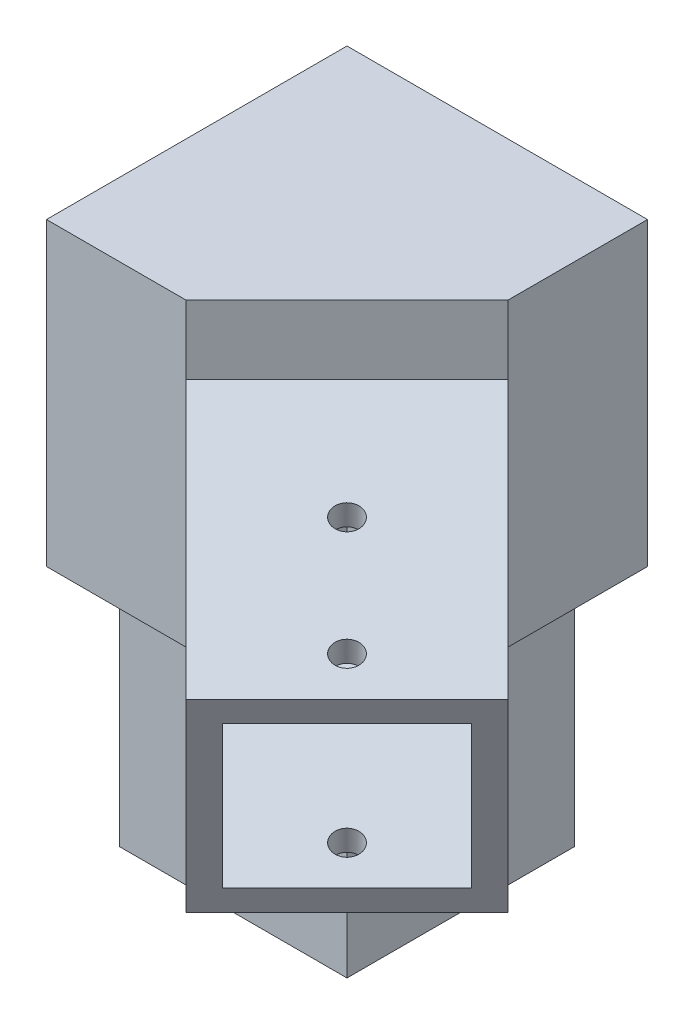
SolidWorks part; units mm, degrees
ref_plane "前视基准面" through (0, 0, 0) normal (0, 0, 1) x (1, 0, 0)
ref_plane "上视基准面" through (0, 0, 0) normal (0, 1, 0) x (1, 0, 0)
ref_plane "右视基准面" through (0, 0, 0) normal (1, 0, 0) x (0, 0, -1)
other "Configuration Table"
sketch "草图2" plane through (0, 0, 0) normal (1, 0, 0) x (0, 0, -1)
  line L0 (0, 0) -> (-60, 0)
  line L1 (-60, 0) -> (-60, -20)
  dimension "D1" = 60
  dimension "D2" = 20
ref_plane "基准面1" through (0, 0, 60) normal (0, 0, 1) x (1, 0, 0)
sketch "草图3" plane through (0, 0, 60) normal (0, 0, 1) x (1, 0, 0)
  line L0 (0, -20) -> (60, -20)
  line L1 (0, 0) -> (0, -20) construction
  line L2 (0, 0) -> (50000, 0) construction
  dimension "D1" = 20
  dimension "D2" = 60
sketch3d "3D草图1"
  line L0 (0, 0, 0) -> (60, -20, 60)
  line L1 (0, 0, 0) -> (0, -20, 0)
  dimension "D1" = 20
sketch "草图4" plane through (0, 0, 0) normal (0, 1, 0) x (1, 0, 0)
  line L1 (-10.25, 10.25) -> (10.25, 10.25)
  line L2 (-10.25, 10.25) -> (-10.25, -10.25)
  line L3 (-10.25, -10.25) -> (10.25, -10.25)
  line L4 (10.25, 10.25) -> (10.25, -10.25)
  line L5 (-10.25, 10.25) -> (10.25, -10.25) construction
  line L6 (-10.25, -10.25) -> (10.25, 10.25) construction
  line L7 (-13.25, 13.25) -> (13.25, 13.25)
  line L8 (-13.25, 13.25) -> (-13.25, -13.25)
  line L9 (-13.25, -13.25) -> (13.25, -13.25)
  line L10 (13.25, 13.25) -> (13.25, -13.25)
  line L11 (-13.25, 13.25) -> (13.25, -13.25) construction
  line L12 (-13.25, -13.25) -> (13.25, 13.25) construction
  point P0 (0, 0)
  point P6 (0, 0)
  dimension "D1" = 20.5
  dimension "D2" = 3
extrude "凸台-拉伸1" add sketch "草图4" against normal blind 50
ref_plane "基准面2" through (0, 0, 0) normal (0.6882, -0.2294, 0.6882) x (0.7255, 0.2176, -0.6529)
sketch "草图5" plane through (0, 0, 0) normal (0.6882, -0.2294, 0.6882) x (0.7255, 0.2176, -0.6529)
  line L0 (-4.7095, -51.6242) -> (18.2639, -4.19)
  line L1 (-7.6985, 12.2824) -> (12.2824, 7.6985)
  line L2 (-7.6985, 12.2824) -> (-12.2824, -7.6985)
  line L3 (-12.2824, -7.6985) -> (7.6985, -12.2824)
  line L4 (12.2824, 7.6985) -> (7.6985, -12.2824)
  line L5 (-7.6985, 12.2824) -> (7.6985, -12.2824) construction
  line L6 (-12.2824, -7.6985) -> (12.2824, 7.6985) construction
  line L7 (-9.9517, 15.8773) -> (15.8773, 9.9517)
  line L8 (-9.9517, 15.8773) -> (-15.8773, -9.9517)
  line L9 (-15.8773, -9.9517) -> (9.9517, -15.8773)
  line L10 (15.8773, 9.9517) -> (9.9517, -15.8773)
  line L11 (-9.9517, 15.8773) -> (9.9517, -15.8773) construction
  line L12 (-15.8773, -9.9517) -> (15.8773, 9.9517) construction
  line L13 (-4.7095, -51.6242) -> (18.2639, -4.19) construction
  line L14 (-18.2639, 4.19) -> (-18.2639, -48.5146)
  line L15 (-18.2639, 4.19) -> (-18.2639, -48.5146) construction
  line L16 (-4.7095, -51.6242) -> (-18.2639, -48.5146) construction
  point P0 (0, 0)
  point P6 (0, 0)
  dimension "D1" = 20.5
  dimension "D2" = 3
extrude "凸台-拉伸2" add sketch "草图5" along normal blind 50
sketch "草图6" plane through (0, 0, 0) normal (0, 1, 0) x (1, 0, 0)
  line L0 (-13.25, 13.25) -> (-13.25, -21.75)
  line L1 (-13.25, -21.75) -> (3.0117, -21.75)
  line L2 (27.1926, -45.931) -> (-7.2197, -11.5186) construction
  line L3 (3.0117, -21.75) -> (21.75, -3.0117)
  line L4 (41.6321, -22.8938) -> (13.25, 5.4883) construction
  line L5 (21.75, -3.0117) -> (21.75, 13.25)
  line L6 (21.75, 13.25) -> (-13.25, 13.25)
  dimension "D1" = 35
extrude "凸台-拉伸3" add sketch "草图6" along normal mid plane 35
extrude "切除-拉伸1" cut sketch "草图4<2>" against normal through all contours L4 L1 L2 L3 region at (0, 0, 0)
sketch "草图4<2>" plane through (0, 0, 0) normal (0, 1, 0) x (1, 0, 0) same geometry as "草图4"
extrude "切除-拉伸2" cut sketch "草图5<2>" along normal through all contours L4 L1 L2 L3 region at (0, 0, 0)
sketch "草图5<2>" plane through (0, 0, 0) normal (0.6882, -0.2294, 0.6882) x (0.7255, 0.2176, -0.6529) same geometry as "草图5"
sketch "草图7" plane through (2.1494, 12.8966, 2.1494) normal (0.1622, 0.9733, 0.1622) x (0.9868, -0.16, -0.0267)
  line L0 (34.8743, -35.8299) -> (34909.1659, -35865.7585) construction
  line L1 (44.3692, -26.5882) -> (25.3794, -45.0716) construction
  circle A0 centre (31.3869, -32.2469) radius 1.6
  circle A1 centre (20.9246, -21.498) radius 1.6
  point P4 (34.8743, -35.8299)
  dimension "D1" = 5
  dimension "D2" = 15
  dimension "D3" = 3.2
extrude "切除-拉伸3" cut sketch "草图7" against normal up to surface (26.5 mm away) up to face at (17.7741, -19.5378, 17.7741)
sketch "草图9" plane through (13.25, 0, 0) normal (1, 0, 0) x (0, 0, -1)
  line L0 (0, -60) -> (0, -50060) construction
  line L1 (-13.25, -50) -> (13.25, -50) construction
  line L2 (-3.0117, -17.5) -> (13.25, -17.5) construction
  circle A0 centre (0, -42.5) radius 1.6
  circle A1 centre (0, -22.5) radius 1.6
  point P4 (0, -50)
  dimension "D1" = 3.2
  dimension "D2" = 5
  dimension "D3" = 20
extrude "切除-拉伸4" cut sketch "草图9" against normal through all
